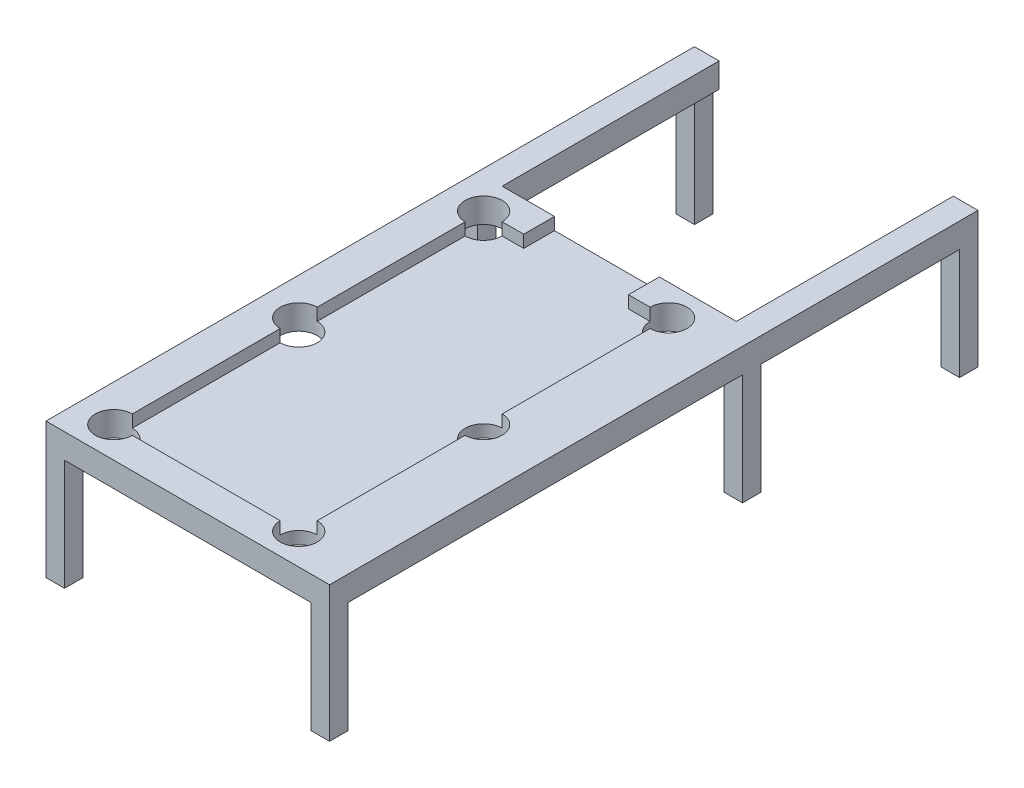
SolidWorks part; units mm, degrees
ref_plane "Front Plane" through (0, 0, 0) normal (0, 0, 1) x (1, 0, 0)
ref_plane "Top Plane" through (0, 0, 0) normal (0, 1, 0) x (1, 0, 0)
ref_plane "Right Plane" through (0, 0, 0) normal (1, 0, 0) x (0, 0, -1)
sketch "Sketch2" plane through (0, 0, 0) normal (0, 1, 0) x (1, 0, 0)
  line L1 (0, 0) -> (460, 0)
  line L2 (0, 0) -> (0, 700)
  line L3 (0, 700) -> (460, 700)
  line L4 (460, 0) -> (460, 700)
  line L5 (60, 50) -> (360, 50)
  line L6 (60, 50) -> (60, 650)
  line L7 (60, 650) -> (360, 650)
  line L8 (360, 50) -> (360, 650)
  dimension "D1" = 700
  dimension "D2" = 460
  dimension "D3" = 600
  dimension "D4" = 300
  dimension "D5" = 60
  dimension "D6" = 50
extrude "Boss-Extrude1" add sketch "Sketch2" along normal blind 20
ref_plane "Plane1" through (0, 0, -700) normal (0, 0, -1) x (-1, 0, 0)
sketch "Sketch10" plane through (0, 0, 0) normal (0, -1, 0) x (1, 0, 0)
  line L1 (0, 0) -> (460, 0)
  line L2 (0, 0) -> (0, -700)
  line L3 (0, -700) -> (460, -700)
  line L4 (460, 0) -> (460, -700)
extrude "Boss-Extrude6" add sketch "Sketch10" along normal blind 20
sketch "Sketch11" plane through (0, -20, 0) normal (0, -1, 0) x (1, 0, 0)
  line L1 (0, 0) -> (30, 0)
  line L2 (0, 0) -> (0, -30)
  line L3 (0, -30) -> (30, -30)
  line L4 (30, 0) -> (30, -30)
  line L5 (460, 0) -> (430, 0)
  line L6 (460, 0) -> (460, -30)
  line L7 (460, -30) -> (430, -30)
  line L8 (430, 0) -> (430, -30)
  line L9 (0, -700) -> (30, -700)
  line L10 (0, -700) -> (0, -670)
  line L11 (0, -670) -> (30, -670)
  line L12 (30, -700) -> (30, -670)
  line L13 (460, -700) -> (430, -700)
  line L14 (460, -700) -> (460, -670)
  line L15 (460, -670) -> (430, -670)
  line L16 (430, -700) -> (430, -670)
  dimension "D1" = 30
extrude "Boss-Extrude7" add sketch "Sketch11" along normal blind 180
sketch "Sketch14" plane through (0, 20, 0) normal (0, 1, 0) x (1, 0, 0)
  line L0 (22, 700) -> (-22, 700) construction
  line L1 (0, 700) -> (40, 700)
  line L2 (0, 700) -> (0, 1052)
  line L3 (0, 1052) -> (40, 1052)
  line L4 (40, 700) -> (40, 1052)
  line L5 (0, 700) -> (0, 0) construction
  line L6 (460, 0) -> (460, 700) construction
  line L7 (460, 700) -> (420, 700)
  line L8 (460, 700) -> (460, 1052)
  line L9 (460, 1052) -> (420, 1052)
  line L10 (420, 700) -> (420, 1052)
  line L11 (330, 1052) -> (390, 1052) construction
  dimension "D3" = 40
  dimension "D4" = 40
extrude "Boss-Extrude8" add sketch "Sketch14" against normal blind 40
sketch "Sketch15" plane through (0, -20, 0) normal (0, -1, 0) x (1, 0, 0)
  line L1 (460, -1052) -> (430, -1052)
  line L2 (460, -1052) -> (460, -1022)
  line L3 (460, -1022) -> (430, -1022)
  line L4 (430, -1052) -> (430, -1022)
  line L6 (0, -1052) -> (30, -1052)
  line L7 (0, -1052) -> (0, -1022)
  line L8 (0, -1022) -> (30, -1022)
  line L9 (30, -1052) -> (30, -1022)
  dimension "D1" = 30
  dimension "D2" = 30
  dimension "D3" = 30
  dimension "D4" = 30
extrude "Boss-Extrude9" add sketch "Sketch15" along normal blind 180
sketch "Sketch17" plane through (0, 20, 0) normal (0, 1, 0) x (1, 0, 0)
  line L0 (60, 650) -> (60, 50) construction
  line L1 (360, 50) -> (360, 650) construction
  circle A0 centre (60, 650) radius 30
  circle A1 centre (60, 350) radius 30
  circle A2 centre (60, 50) radius 30
  circle A3 centre (360, 50) radius 30
  circle A4 centre (360, 350) radius 30
  circle A5 centre (360, 650) radius 30
  line M15 (60, 50) -> (60, 650)
  line M16 (60, 650) -> (360, 650)
  line M17 (360, 650) -> (360, 50)
  line M18 (360, 50) -> (60, 50)
  dimension "D1" = 60
extrude "Cut-Extrude1" cut sketch "Sketch17" against normal blind 60 contours A5 M17 M16 | A4 M17 | A3 M18 M17 | A1 M15 | A1 M15 | A2 M15 M18 | A2 M18 M15 | A3 M17 M18 | A5 M16 M17 | A4 M17 | A0 region at (347.2676, 20, -637.2676) region at (364.2441, 20, -654.2441) region at (47.2676, 20, -350) region at (72.7324, 20, -350) region at (347.2676, 20, -350) region at (372.7324, 20, -350) region at (55.7559, 20, -45.7559) region at (72.7324, 20, -62.7324) region at (347.2676, 20, -62.7324) region at (364.2441, 20, -45.7559)
sketch "Sketch18" plane through (0, 20, 0) normal (0, 1, 0) x (1, 0, 0)
  line L9 (330, 650) -> (90, 650) construction
  line L10 (420, 700) -> (40, 700) construction
  line L11 (210, 700) -> (295, 700)
  line L12 (295, 700) -> (295, 650)
  line L13 (330, 650) -> (90, 650) construction
  line L14 (210, 650) -> (295, 650)
  line L15 (210, 700) -> (125, 700)
  line L16 (125, 700) -> (125, 650)
  line L17 (125, 650) -> (210, 650)
  dimension "D1" = 85
  dimension "D2" = 85
  dimension "D3" = 35
extrude "Cut-Extrude2" cut sketch "Sketch18" against normal blind 20
sketch "Sketch19" plane through (125, 0, 0) normal (1, 0, 0) x (0, 0, -1)
  line L0 (650, 0) -> (652.5, 0) construction
  line L1 (700, 0) -> (650, 0) construction
  line L2 (652.5, 0) -> (652.5, 2.5) construction
  line L4 (652.5, 2.5) -> (650, 2.5)
  line L5 (652.5, 2.5) -> (652.5, 0)
  line L6 (652.5, 0) -> (650, 0)
  line L7 (650, 2.5) -> (650, 0)
  point P8 (652.5, 2.5)
  dimension "D1" = 2.5
  dimension "D2" = 2.5
